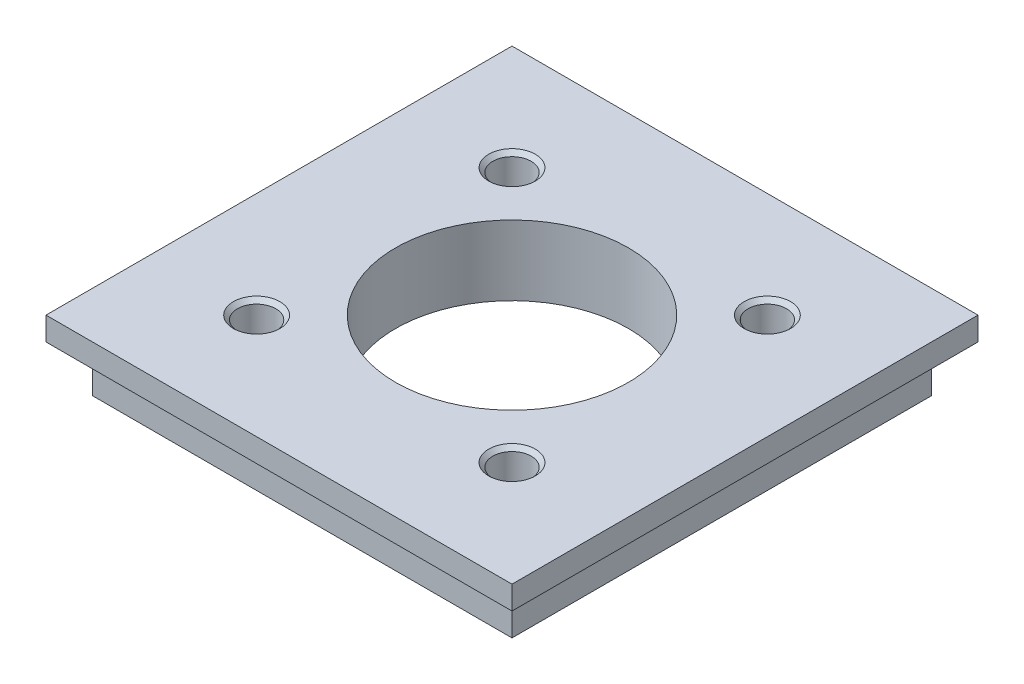
SolidWorks part; units mm, degrees
ref_plane "Front Plane" through (0, 0, 0) normal (0, 0, 1) x (1, 0, 0)
ref_plane "Top Plane" through (0, 0, 0) normal (0, 1, 0) x (1, 0, 0)
ref_plane "Right Plane" through (0, 0, 0) normal (1, 0, 0) x (0, 0, -1)
sketch "Sketch1" plane through (0, 0, 0) normal (0, 1, 0) x (1, 0, 0)
  line L1 (-20, -20) -> (20, -20)
  line L2 (-20, -20) -> (-20, 20)
  line L3 (-20, 20) -> (20, 20)
  line L4 (20, -20) -> (20, 20)
  line L5 (-20, -20) -> (20, 20) construction
  line L6 (-20, 20) -> (20, -20) construction
  point P0 (0, 0)
  dimension "D1" = 40
extrude "Boss-Extrude1" add sketch "Sketch1" along normal blind 2
sketch "Sketch2" plane through (-20, 0, 0) normal (-1, 0, 0) x (0, 0, 1)
  line L0 (-20, 1) -> (20, 1) construction
  line L1 (-20, 2) -> (-20, 0) construction
  line L2 (20, 2) -> (20, 0) construction
  point P8 (-10, 1)
  point P10 (10, 1)
  dimension "D1" = 10
  dimension "D2" = 10
hole_wizard "Tap Drill for M4 Tap1" [suppressed] positions "Sketch2" profile "Sketch3" hole size "M4" standard "DIN"
sketch "Sketch3" plane through (-18, 4, 8) normal (0, 1, 0) x (0, 0, 1)
  line L0 (0, 0) -> (0, 36)
  line L1 (0, 36) -> (1.65, 36)
  line L2 (1.65, 36) -> (1.65, 0)
  line L5 (1.65, 0) -> (0, 0)
  line L11 (0, -6.35) -> (0, 107.95) construction
  dimension "Thru Hole Dia." = 3.3
  dimension "Thru Hole Depth" = 36
sketch "Sketch4" plane through (0, 0, 0) normal (0, -1, 0) x (-1, 0, 0)
  point P0 (0, 0)
hole_wizard "Ø25.0mm Dowel Hole1" positions "Sketch4" profile "Sketch5" hole size "Ø25.0" standard "DIN" end condition through all
sketch "Sketch5" plane through (0, 0, 0) normal (1, 0, 0) x (0, 0, -1)
  line L0 (0, 0) -> (0, 2)
  line L1 (0, 2) -> (10, 2)
  line L2 (10, 2) -> (10, 0)
  line L5 (10, 0) -> (0, 0)
  line L11 (0, -6.35) -> (0, 107.95) construction
  dimension "Thru Hole Dia." = 20
  dimension "Thru Hole Depth" = 2
sketch "Sketch9" plane through (0, 0, 0) normal (0, -1, 0) x (1, 0, 0)
  line L8 (18, -18) -> (18, 18)
  line L9 (18, 18) -> (-18, 18)
  line L10 (-18, 18) -> (-18, -18)
  line L11 (-18, -18) -> (18, -18)
  line L12 (18, -18) -> (18, 18)
  line L13 (18, 18) -> (-18, 18)
  line L14 (-18, 18) -> (-18, -18)
  line L15 (-18, -18) -> (18, -18)
  circle A0 centre (0, 0) radius 10 construction
  circle A1 centre (0, 0) radius 10
  dimension "D1" = 2
extrude "Boss-Extrude2" add sketch "Sketch9" along normal blind 4
sketch "Sketch6" plane through (0, 2, 0) normal (0, 1, 0) x (1, 0, 0)
  line L0 (0, 0) -> (10.9602, 10.9602) construction
  circle A0 centre (0, 0) radius 15.5
  point P7 (10.9602, 10.9602)
  point P13 (10.9602, 10.9602)
  point P20 (10.9602, -10.9602)
  point P21 (-10.9602, -10.9602)
  point P22 (-10.9602, 10.9602)
  dimension "D1" = 31
  dimension "D2" = 4
hole_wizard "Tap Drill for M4 Tap2" positions "Sketch6" profile "Sketch8" hole size "M4" standard "DIN" end condition through all
sketch "Sketch8" plane through (-10.9602, 2, -10.9602) normal (1, 0, 0) x (0, 0, 1)
  line L0 (0, 0) -> (0, 6)
  line L1 (0, 6) -> (1.65, 6)
  line L2 (1.65, 6) -> (1.65, 0.35)
  line L3 (1.65, 0.35) -> (2, 0)
  line L5 (2, 0) -> (0, 0)
  line L6 (-1.65, 0.35) -> (-2, 0) construction
  line L11 (0, -6.35) -> (0, 107.95) construction
  dimension "Thru Hole Dia." = 3.3
  dimension "Thru Hole Depth" = 6
  dimension "Near C'Sink Dia." = 4
  dimension "Near C'Sink Angle" = 90
